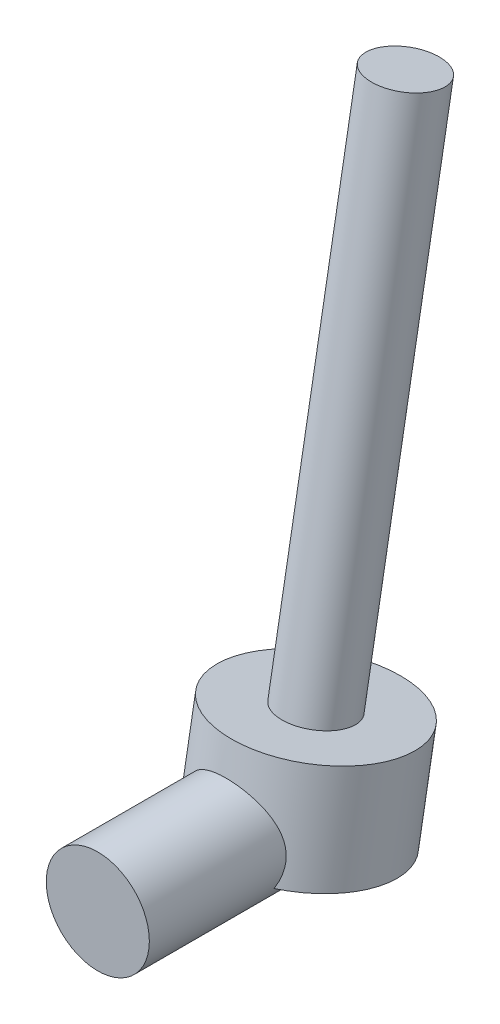
SolidWorks part; units mm, degrees
ref_plane "Front Plane" through (0, 0, 0) normal (0, 0, 1) x (1, 0, 0)
ref_plane "Top Plane" through (0, 0, 0) normal (0, 1, 0) x (1, 0, 0)
ref_plane "Right Plane" through (0, 0, 0) normal (1, 0, 0) x (0, 0, -1)
sketch "Sketch1" plane through (0, 0, 0) normal (0, 0, 1) x (1, 0, 0)
  circle A0 centre (0, 0) radius 30
  dimension "D1" = 60
extrude "Boss-Extrude1" add sketch "Sketch1" along normal blind 120
ref_axis "Axis1" through (-33, 0, 0) along (1, 0, 0)
ref_plane "Plane1" through (0, 0, 0) normal (0, 0.9848, -0.1736) x (-1, 0, 0)
sketch "Sketch2" plane through (0, 0, 0) normal (0, 0.9848, -0.1736) x (-1, 0, 0)
  circle A0 centre (0, 0) radius 50
  dimension "D1" = 100
extrude "Boss-Extrude2" add sketch "Sketch2" along normal blind 40 and the other way blind 20
sketch "Sketch3" plane through (0, 39.3923, -6.9459) normal (0, 0.9848, -0.1736) x (1, 0, 0)
  circle A0 centre (0, 0) radius 20
  circle A1 centre (0, 0) radius 50 construction
  dimension "D1" = 40
extrude "Boss-Extrude3" add sketch "Sketch3" along normal blind 300
